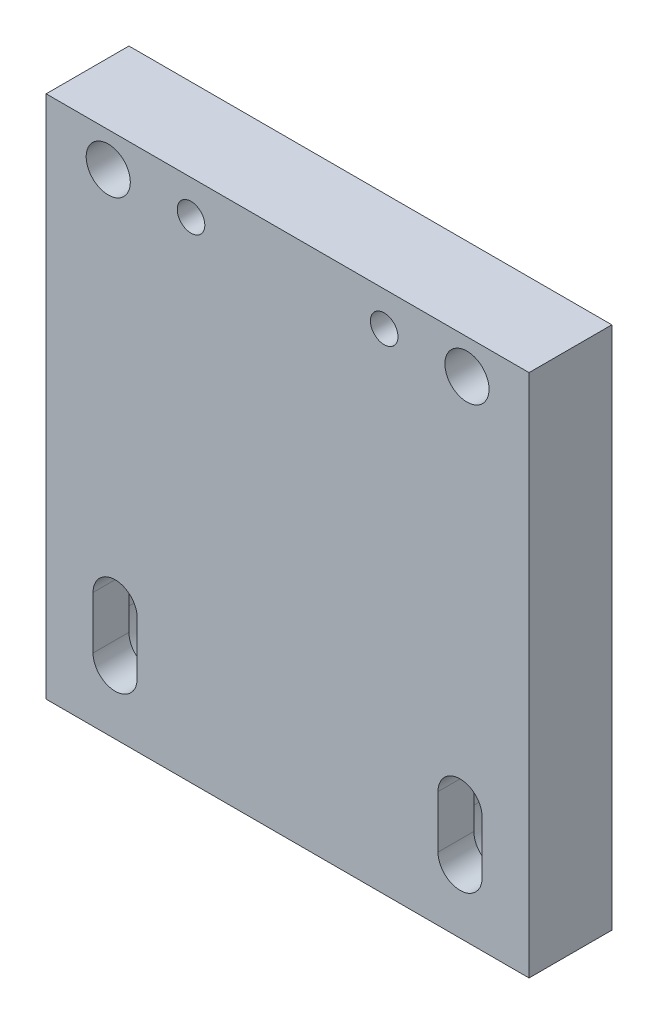
SolidWorks part; units mm, degrees
ref_plane "Front Plane" through (0, 0, 0) normal (0, 0, 1) x (1, 0, 0)
ref_plane "Top Plane" through (0, 0, 0) normal (0, 1, 0) x (1, 0, 0)
ref_plane "Right Plane" through (0, 0, 0) normal (1, 0, 0) x (0, 0, -1)
sketch "Sketch1" plane through (0, 0, 0) normal (0, 1, 0) x (1, 0, 0)
  line L1 (0, 0) -> (35, 0)
  line L2 (0, 0) -> (0, 6)
  line L3 (0, 6) -> (35, 6)
  line L4 (35, 0) -> (35, 6)
  dimension "D1" = 6
  dimension "D2" = 35
extrude "Boss-Extrude1" add sketch "Sketch1" along normal blind 38
sketch "Sketch2" plane through (0, 0, 0) normal (0, 0, 1) x (1, 0, 0)
  line L0 (17.5, 38) -> (17.5, 0) construction
  line L1 (0, 38) -> (35, 38) construction
  line L2 (0, 0) -> (35, 0) construction
  circle A0 centre (4.5, 35.5) radius 1.6
  circle A1 centre (30.5, 35.5) radius 1.6
  dimension "D3" = 3.2
  dimension "D1" = 2.5
  dimension "D2" = 2.5
  dimension "D4" = 13
  dimension "D5" = 13
extrude "Cut-Extrude1" cut sketch "Sketch2" against normal through all
sketch "Sketch3" plane through (0, 0, 0) normal (0, 0, 1) x (1, 0, 0)
  line L0 (17.5, 38) -> (17.5, 0) construction
  line L1 (0, 38) -> (35, 38) construction
  line L2 (0, 0) -> (35, 0) construction
  circle A0 centre (10.5, 35.5) radius 1
  circle A1 centre (24.5, 35.5) radius 1
  dimension "D5" = 2
  dimension "D1" = 7
  dimension "D2" = 7
  dimension "D3" = 2.5
  dimension "D4" = 2.5
extrude "Cut-Extrude2" cut sketch "Sketch3" against normal blind 4
hole_wizard "CBORE SLOT for M3 Hex Socket Head Cap Screw1" positions "Sketch4" profile "Sketch6" size "M3" standard "DIN" slot yes end condition through all
sketch "Sketch4" plane through (0, 0, -6) normal (0, 0, -1) x (-1, 0, 0)
  line L0 (-30, 3) -> (-30, 10) construction
  line L1 (-35, 38) -> (-35, 0) construction
  line L2 (-35, 0) -> (0, 0) construction
  line L3 (0, 38) -> (0, 0) construction
  point P0 (-30, 6.5)
  point P4 (-5, 6.5)
  point P7 (-28.078, 7.7852)
  dimension "D1" = 7
  dimension "D2" = 5
  dimension "D3" = 6.5
  dimension "D4" = 6.5
  dimension "D5" = 5
sketch "Sketch6" plane through (30, 6.5, -6) normal (1, 0, 0) x (0, 1, 0)
  line L0 (0, 0) -> (0, 6)
  line L1 (0, 6) -> (1.6, 6)
  line L3 (1.6, 6) -> (1.6, 3.4)
  line L4 (1.6, 3.4) -> (3.25, 3.4)
  line L5 (3.25, 3.4) -> (3.25, 0)
  line L7 (3.25, 0) -> (0, 0)
  line L11 (0, -6.35) -> (0, 107.95) construction
  dimension "Thru Hole Dia." = 3.2
  dimension "Thru Hole Depth" = 6
  dimension "C'Bore Dia." = 6.5
  dimension "C'Bore Depth" = 3.4
ref_plane "Plane1" through (17.5, 0, 0) normal (1, 0, 0) x (0, 0, -1)
